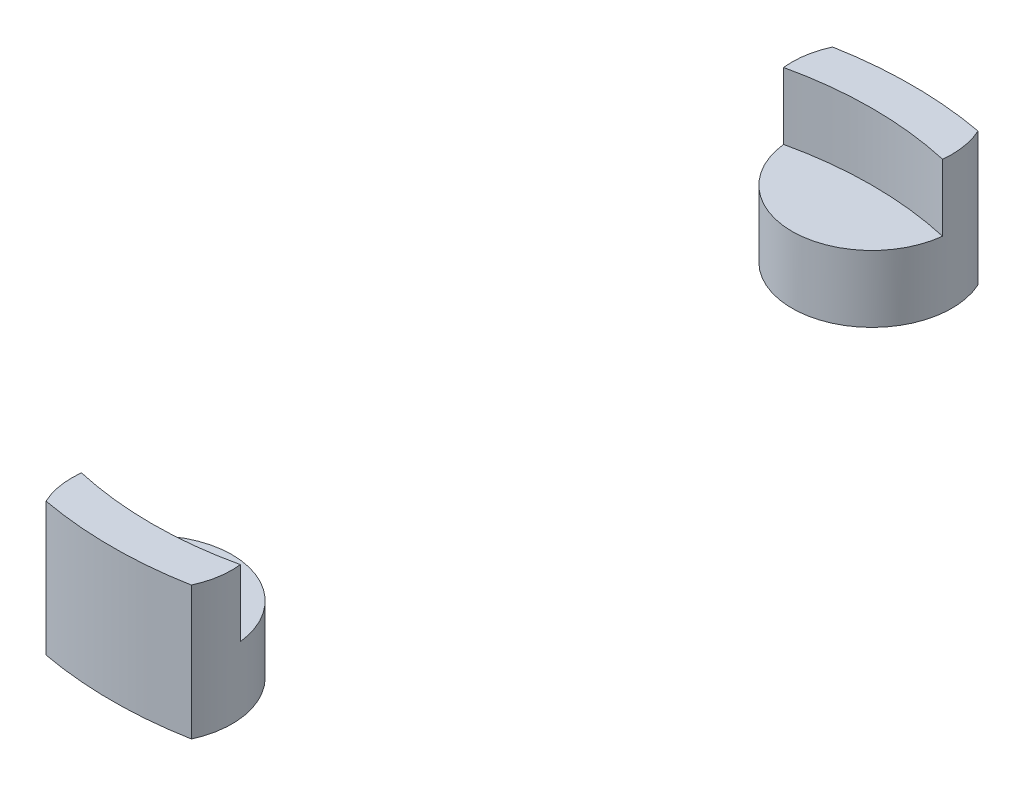
SolidWorks part; units mm, degrees
ref_plane "Front Plane" through (0, 0, 0) normal (0, 0, 1) x (1, 0, 0)
ref_plane "Top Plane" through (0, 0, 0) normal (0, 1, 0) x (1, 0, 0)
ref_plane "Right Plane" through (0, 0, 0) normal (1, 0, 0) x (0, 0, -1)
sketch "Sketch2" plane through (0, 0, 0) normal (0, 1, 0) x (1, 0, 0)
  line L0 (0, 15) -> (0, -15) construction
  circle A0 centre (0, 0) radius 13.5
  circle A1 centre (0, 0) radius 15
  arc A2 (-2.7272, 14.75) -> (2.7272, 14.75) centre (0, 13.5) ccw
  arc A3 (2.7272, -14.75) -> (-2.7272, -14.75) centre (0, -13.5) ccw
  dimension "D1" = 27
  dimension "D2" = 30
  dimension "D3" = 6
  dimension "D4" = 6
extrude "Boss-Extrude2" add sketch "Sketch2" along normal blind 5 contours L0 A1 A2 A0 | A1 L0 A0 A2 | L0 A0 A3 A1 | A0 L0 A1 A3 region at (1.4716, 0, -14.137) region at (-1.4716, 0, -14.137) region at (-1.4716, 0, 14.137) region at (1.4716, 0, 14.137)
extrude "Boss-Extrude3" add sketch "Sketch2<6>" along normal blind 2.5 contours A0 L0 A2 | L0 A0 A2 | A3 L0 A0 | L0 A3 A0 region at (1.225, 0, -12.1686) region at (-1.225, 0, -12.1686) region at (1.225, 0, 12.1686) region at (-1.225, 0, 12.1686)
sketch "Sketch2<6>" plane through (0, 0, 0) normal (0, 1, 0) x (1, 0, 0) same geometry as "Sketch2"
